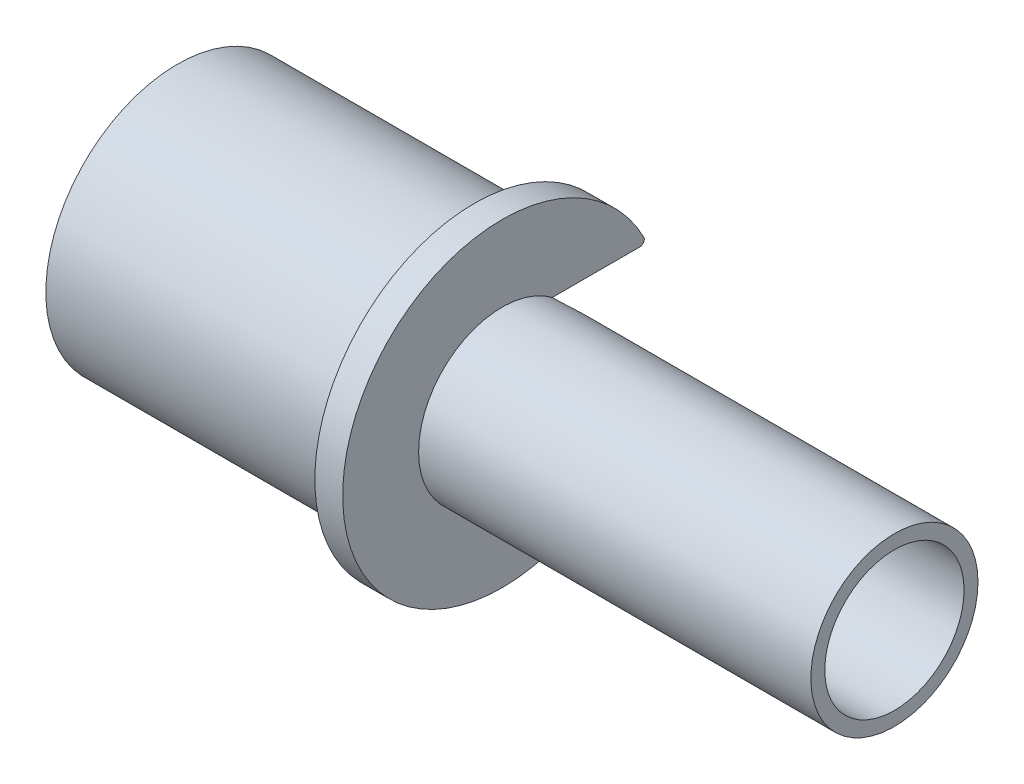
SolidWorks part; units mm, degrees
material "6061-T6 (SS)"
ref_plane "Front Plane" through (0, 0, 0) normal (0, 0, 1) x (1, 0, 0)
ref_plane "Top Plane" through (0, 0, 0) normal (0, 1, 0) x (1, 0, 0)
ref_plane "Right Plane" through (0, 0, 0) normal (1, 0, 0) x (0, 0, -1)
sketch "Sketch1" plane through (0, 0, 0) normal (0, 0, 1) x (1, 0, 0)
  line L0 (0, 0) -> (-16.6687, 0) construction
  line L1 (-1.4625, 3.9687) -> (-1.4625, 4.7625)
  line L2 (-1.4625, 4.7625) -> (-23.8125, 4.7625)
  line L3 (-23.8125, 4.7625) -> (-23.8125, 9.0875)
  line L4 (-23.8125, 9.0875) -> (-25.4, 9.0875)
  line L5 (-25.4, 9.0875) -> (-25.4, 7.5)
  line L6 (-25.4, 7.5) -> (-42.315, 7.5)
  line L7 (-42.315, 7.5) -> (-42.315, 3.9687)
  line L8 (-42.315, 3.9687) -> (-1.4625, 3.9687)
  line L9 (-25.4, -15.27) -> (-25.4, 15.27) construction
  line L10 (-50.8, -5.5563) -> (-50.8, 5.5562) construction
  line L14 (-1.4625, -11.375) -> (-1.4625, 11.375) construction
  dimension "D1" = 7.9375
  dimension "D4" = 15
  dimension "D3" = 9.525
  dimension "D2" = 1.5875
  dimension "D5" = 1.5875
  dimension "D6" = 8.485
revolve "Revolve1" add sketch "Sketch1" angle 360 about L0
sketch "Sketch2" plane through (-1.4625, 0, 0) normal (1, 0, 0) x (0, 0, -1)
  line L0 (1.3441, 3.7342) -> (8.2848, 3.7342)
  line L1 (8.2848, -3.7342) -> (1.3441, -3.7342)
  line L2 (0, 0) -> (14.3216, 0) construction
  circle A0 centre (0, 0) radius 3.9687 construction
  circle A1 centre (0, 0) radius 9.0875 construction
  arc A2 (1.3441, 3.7342) -> (1.3441, -3.7342) centre (0, 0) cw
  arc A3 (8.2848, 3.7342) -> (8.2848, -3.7342) centre (0, 0) cw
  arc A4 (3.6742, 3.7342) -> (3.6742, -3.7342) centre (0, 0) cw construction
  circle A5 centre (5.2387, 0) radius 1.27 construction
  circle A6 centre (4.623, 2.4642) radius 1.27 construction
  circle A7 centre (4.623, -2.4642) radius 1.27 construction
  dimension "D1" = 1.27
  dimension "D2" = 2.54
extrude "Cut-Extrude1" [suppressed] cut sketch "Sketch2" against normal through all both
sketch "Sketch3" plane through (0, 0, 0) normal (0, 0, 1) x (1, 0, 0)
  line L0 (-42.315, 3.81) -> (-42.315, -3.81)
  line L1 (-42.315, 7.5) -> (-42.315, -7.5) construction
  line L2 (-42.315, -3.81) -> (-23.8125, -3.81)
  line L4 (-23.8125, 3.81) -> (-42.315, 3.81)
  line L5 (-20.6375, -0.635) -> (-20.6375, 0.635)
  line L6 (-20.6375, 0) -> (0, 0) construction
  line L8 (-23.8125, -9.0875) -> (-23.8125, 9.0875) construction
  arc A1 (-23.8125, -3.81) -> (-20.6375, -0.635) centre (-23.8125, -0.635) ccw
  arc A2 (-20.6375, 0.635) -> (-23.8125, 3.81) centre (-23.8125, 0.635) ccw
  dimension "D1" = 7.62
  dimension "D2" = 3.175
extrude "Cut-Extrude2" cut sketch "Sketch3" against normal up to next
fillet "Fillet1" radius 0.254 4 edges at (-24.6062, 3.81, -8.2502) (-24.6062, -3.81, -8.2502) (-33.8575, -3.81, -6.4602) (-33.8575, 3.81, -6.4602)
equation "\"bearing1\"=0.273438"
equation "\"D1@Sketch1\"=5/16"
equation "\"D4@Sketch1\"=15mm"
equation "\"D6@Sketch1\"=.275+1.5mm"
